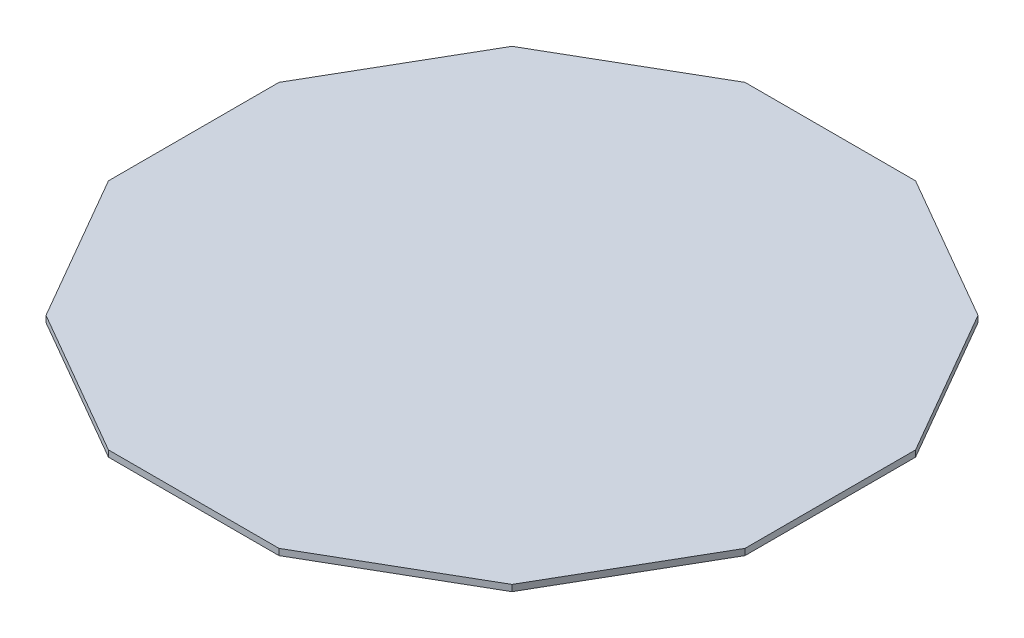
SolidWorks part; units mm, degrees
material "ABS PC"
ref_plane "Front Plane" through (0, 0, 0) normal (0, 0, 1) x (1, 0, 0)
ref_plane "Top Plane" through (0, 0, 0) normal (0, 1, 0) x (1, 0, 0)
ref_plane "Right Plane" through (0, 0, 0) normal (1, 0, 0) x (0, 0, -1)
sketch "Sketch1" plane through (0, 0, 0) normal (0, 1, 0) x (1, 0, 0)
  line L0 (39.444, 147.2071) -> (-39.444, 147.2071)
  line L1 (-39.444, 147.2071) -> (-107.7631, 107.7631)
  line L2 (-107.7631, 107.7631) -> (-147.2071, 39.444)
  line L3 (-147.2071, 39.444) -> (-147.2071, -39.444)
  line L4 (-147.2071, -39.444) -> (-107.7631, -107.7631)
  line L5 (-107.7631, -107.7631) -> (-39.444, -147.2071)
  line L6 (-39.444, -147.2071) -> (39.444, -147.2071)
  line L7 (39.444, -147.2071) -> (107.7631, -107.7631)
  line L8 (107.7631, -107.7631) -> (147.2071, -39.444)
  line L9 (147.2071, -39.444) -> (147.2071, 39.444)
  line L10 (147.2071, 39.444) -> (107.7631, 107.7631)
  line L11 (107.7631, 107.7631) -> (39.444, 147.2071)
  circle A0 centre (0, 0) radius 152.4
  dimension "D1" = 304.8
extrude "Boss-Extrude1" add sketch "Sketch1" against normal blind 2.921 contours L10 L11 L0 L1 L2 L3 L4 L5 L6 L7 L8 L9 region at (0, 0, 0)
